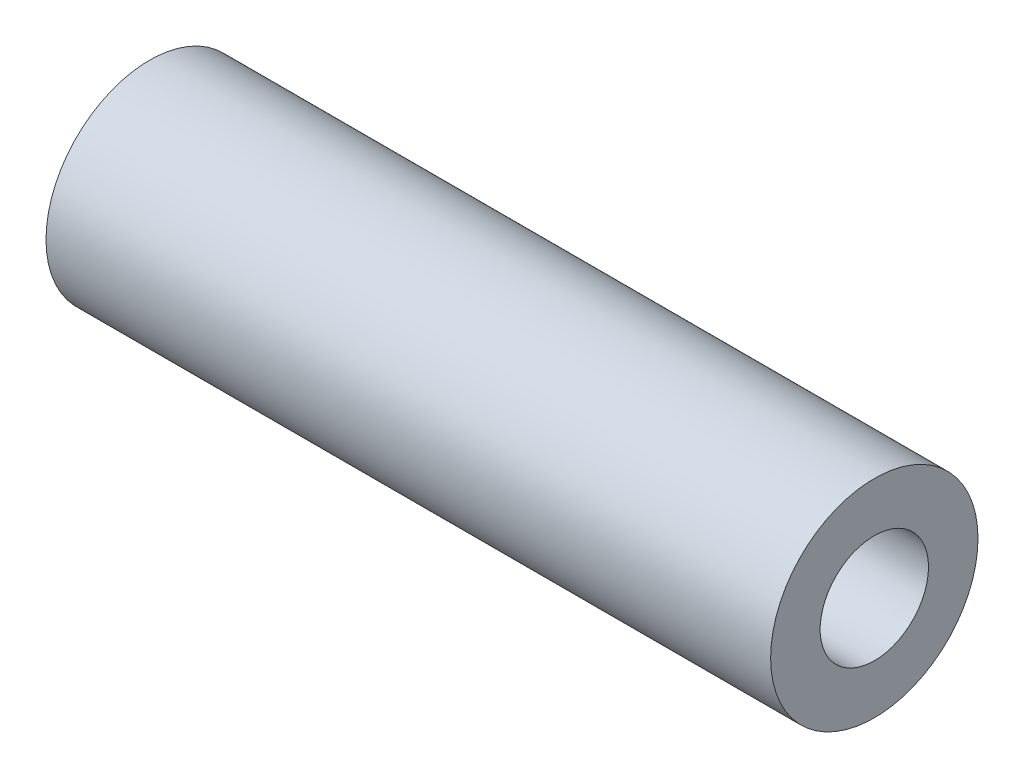
SolidWorks part; units mm, degrees
material "6061-T6 (SS)"
ref_plane "Front Plane" through (0, 0, 0) normal (0, 0, 1) x (1, 0, 0)
ref_plane "Top Plane" through (0, 0, 0) normal (0, 1, 0) x (1, 0, 0)
ref_plane "Right Plane" through (0, 0, 0) normal (1, 0, 0) x (0, 0, -1)
sketch "Sketch1" plane through (0, 0, 0) normal (1, 0, 0) x (0, 0, -1)
  circle A0 centre (0, 0) radius 4.7625
  circle A1 centre (0, 0) radius 2.4892
  dimension "D1" = 4.9784
  dimension "D2" = 9.525
extrude "Boss-Extrude1" add sketch "Sketch1" along normal mid plane 33.2867
